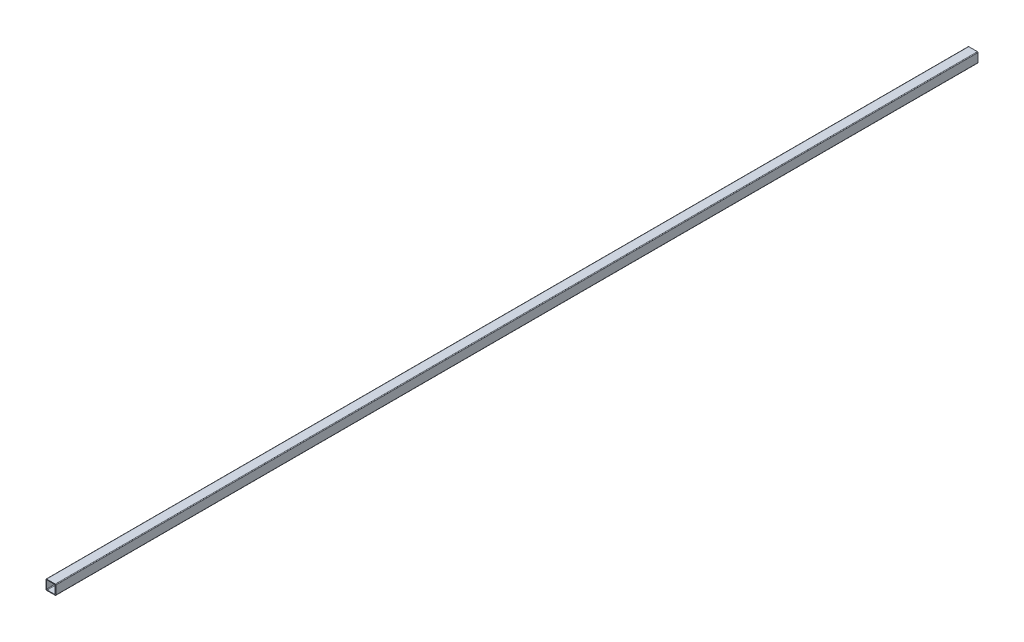
SolidWorks part; units mm, degrees
material "Hexcel AS4C (3000 Filaments)"
ref_plane "Front Plane" through (0, 0, 0) normal (0, 0, 1) x (1, 0, 0)
ref_plane "Top Plane" through (0, 0, 0) normal (0, 1, 0) x (1, 0, 0)
ref_plane "Right Plane" through (0, 0, 0) normal (1, 0, 0) x (0, 0, -1)
sketch "Sketch1" plane through (0, 0, 0) normal (0, 0, 1) x (1, 0, 0)
  line L1 (-4, 4) -> (4, 4)
  line L2 (-4, 4) -> (-4, -4)
  line L3 (-4, -4) -> (4, -4)
  line L4 (4, 4) -> (4, -4)
  line L5 (-4, 4) -> (4, -4) construction
  line L6 (-4, -4) -> (4, 4) construction
  line L7 (-3.5, 3.5) -> (3.5, 3.5)
  line L8 (-3.5, 3.5) -> (-3.5, -3.5)
  line L9 (-3.5, -3.5) -> (3.5, -3.5)
  line L10 (3.5, 3.5) -> (3.5, -3.5)
  line L11 (-3.5, 3.5) -> (3.5, -3.5) construction
  line L12 (-3.5, -3.5) -> (3.5, 3.5) construction
  point P0 (0, 0)
  point P6 (0, 0)
  point P11 (0, 0)
  dimension "D1" = 8
  dimension "D2" = 0.5
extrude "Boss-Extrude1" add sketch "Sketch1" along normal mid plane 750
fillet "Fillet1" radius 0.5 8 edges at (4, 4, 0) (3.5, 3.5, 0) (4, -4, 0) (3.5, -3.5, 0) (-4, -4, 0) (-3.5, -3.5, 0) (-3.5, 3.5, 0) (-4, 4, 0)
